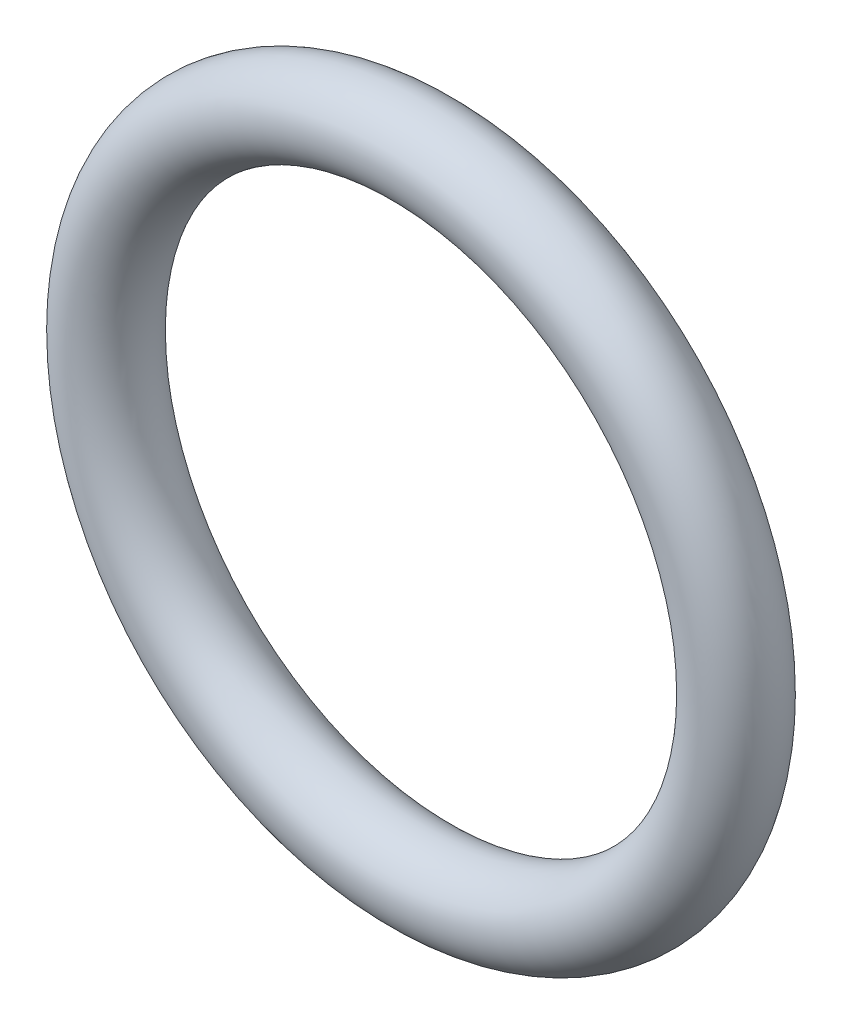
SolidWorks part; units mm, degrees
ref_plane "Front Plane" through (0, 0, 0) normal (0, 0, 1) x (1, 0, 0)
ref_plane "Top Plane" through (0, 0, 0) normal (0, 1, 0) x (1, 0, 0)
ref_plane "Right Plane" through (0, 0, 0) normal (1, 0, 0) x (0, 0, -1)
sketch "Sketch1" plane through (0, 0, 0) normal (0, 0, 1) x (1, 0, 0)
  line L0 (-4.25, 0) -> (4.25, 0) construction
  circle A0 centre (0, 0) radius 4.25
  circle A1 centre (0, 0) radius 3.25
  point P4 (3.25, 0)
  point P5 (4.25, 0)
  point P8 (0, 0)
  point P9 (0, 4.25)
  point P10 (0, -4.25)
  dimension "ID" = 6.5
  dimension "Width" = 1
  dimension "OD" = 8.5
sketch "Sketch2" plane through (0, 0, 0) normal (0, 1, 0) x (1, 0, 0)
  line L0 (-4.25, 0) -> (4.25, 0) construction
  line L1 (0, 0.5) -> (0, -0.5) construction
  circle A0 centre (3.75, 0) radius 0.5
  point P8 (0, 0)
  point P11 (3.75, 0.5)
revolve "Revolve1" add sketch "Sketch2" angle 360 about L1
sketch "Sketch3" plane through (0, 0, 0) normal (1, 0, 0) x (0, 0, -1)
  line L0 (-0.5, 0) -> (0.5, 0) construction
  line L1 (0.5, -3.75) -> (0.5, 3.75) construction
  line L3 (-0.5, 4.25) -> (0.5, 4.25) construction
  line L4 (-0.5, 4.25) -> (-0.5, -4.25) construction
  line L5 (-0.5, -4.25) -> (0.5, -4.25) construction
  line L6 (0.5, 4.25) -> (0.5, -4.25) construction
  point P2 (0, 0)
ref_axis "Axis1" through (0, 0, 0.55) along (0, 0, -1)
